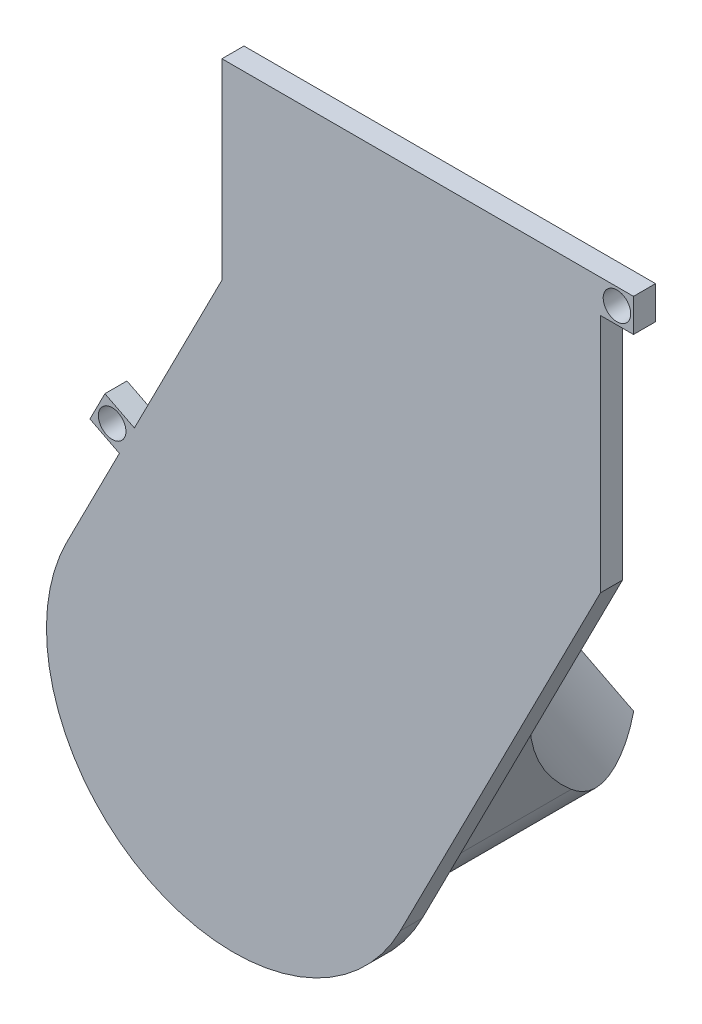
SolidWorks part; units mm, degrees
ref_plane "Front Plane" through (0, 0, 0) normal (0, 0, 1) x (1, 0, 0)
ref_plane "Top Plane" through (0, 0, 0) normal (0, 1, 0) x (1, 0, 0)
ref_plane "Right Plane" through (0, 0, 0) normal (1, 0, 0) x (0, 0, -1)
sketch "Sketch2" plane through (0, 0, 0) normal (0, 0, 1) x (1, 0, 0)
  line L0 (-107.4226, -83.8012) -> (-114.2121, -80.3418)
  line L1 (-87.2427, 0) -> (0, 0)
  line L2 (0, -7.62) -> (0, -62.992)
  line L3 (0, -62.992) -> (-46.1254, -153.5183)
  line L4 (-87.2427, 0) -> (-87.2427, -44.196)
  line L5 (-87.2427, -44.196) -> (-107.4226, -83.8012)
  line L6 (-114.2121, -80.3418) -> (-117.6715, -87.1313)
  line L7 (-117.6715, -87.1313) -> (-110.882, -90.5907)
  line L8 (0, 0) -> (7.62, 0)
  line L9 (7.62, 0) -> (7.62, -7.62)
  line L10 (7.62, -7.62) -> (0, -7.62)
  line L11 (-110.882, -90.5907) -> (-122.9899, -114.3539)
  arc A3 (-122.9899, -114.3539) -> (-46.1254, -153.5183) centre (-84.5577, -133.9361) ccw
  circle A4 centre (3.81, -3.81) radius 3.175
  circle A5 centre (-112.547, -85.4663) radius 3.175
  dimension "D2" = 7.62
  dimension "D3" = 6.35
  dimension "D4" = 3.81
  dimension "D11" = 101.6
  dimension "D14" = 6.35
  dimension "D16" = 3.81
  dimension "D5" = 3.81
  dimension "D6" = 7.62
  dimension "D7" = 7.62
  dimension "D8" = 7.62
  dimension "D9" = 153
  dimension "D10" = 55.372
  dimension "D12" = 78.74
  dimension "D13" = 7.62
  dimension "D15" = 3.81
  dimension "D17" = 44.45
  dimension "D18" = 44.196
extrude "Boss-Extrude1" add sketch "Sketch2" along normal blind 5.08
sketch "Sketch3" plane through (0, 0, 0) normal (0, 0, -1) x (-1, 0, 0)
  line L22 (117.332, -117.2367) -> (80.8927, -45.7205)
  line L23 (80.8927, -45.7205) -> (80.8927, -6.35)
  line L24 (80.8927, -6.35) -> (6.35, -6.35)
  line L25 (6.35, -6.35) -> (6.35, -61.4675)
  line L26 (6.35, -61.4675) -> (51.7833, -150.6354)
  line L27 (117.332, -117.2367) -> (80.8927, -45.7205)
  line L28 (80.8927, -45.7205) -> (80.8927, -6.35)
  line L29 (80.8927, -6.35) -> (6.35, -6.35)
  line L30 (6.35, -6.35) -> (6.35, -61.4675)
  line L31 (6.35, -61.4675) -> (51.7833, -150.6354)
  arc A2 (51.7833, -150.6354) -> (117.332, -117.2367) centre (84.5577, -133.9361) ccw
  arc A3 (51.7833, -150.6354) -> (117.332, -117.2367) centre (84.5577, -133.9361) ccw
  dimension "D1" = 6.35
extrude "Boss-Extrude2" add sketch "Sketch3" along normal blind 82.55
sketch "Sketch4" plane through (-6.35, 0, 0) normal (1, 0, 0) x (0, 0, -1)
  line L0 (0, -6.35) -> (82.55, -6.35)
  line L1 (82.55, -6.35) -> (82.55, 41.3103)
  line L2 (82.55, 41.3103) -> (0, -6.35)
  dimension "D1" = 60
extrude "Boss-Extrude3" add sketch "Sketch4" against normal up to surface (74.5427 mm away) up to face at (-80.8927, -26.0353, -41.275)
sketch "Sketch6" plane through (-45.7258, 23.2985, 0) normal (-0.891, 0.454, 0) x (0, 0, 1)
  line L0 (-82.55, -157.7263) -> (-82.55, -194.5098) construction
  line L1 (0, -77.4618) -> (0, 65.8402)
  line L2 (0, 65.8402) -> (-82.55, 65.8402)
  line L3 (-82.55, 65.8402) -> (-82.55, -188.1598)
  arc A0 (0, -77.4618) -> (-82.55, -188.1598) centre (-145.5997, -55.0135) cw
  dimension "D1" = 6.35
  dimension "D2" = 147.32
  dimension "D3" = 254
extrude "Cut-Extrude2" cut sketch "Sketch6" against normal mid plane 203.2
